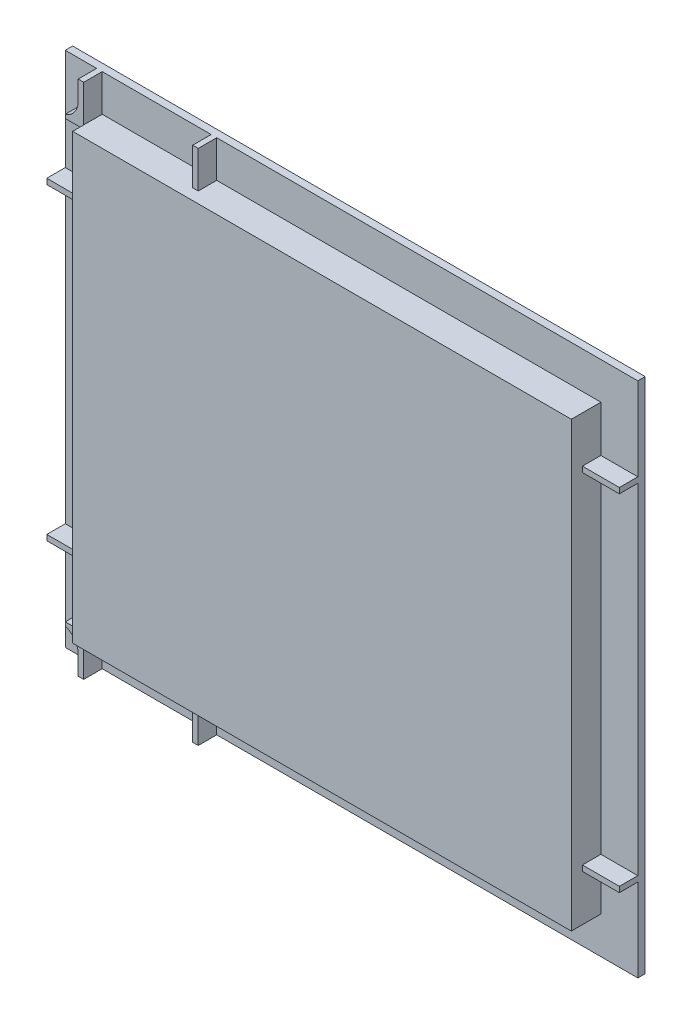
SolidWorks part; units mm, degrees
ref_plane "Front Plane" through (0, 0, 0) normal (0, 0, 1) x (1, 0, 0)
ref_plane "Top Plane" through (0, 0, 0) normal (0, 1, 0) x (1, 0, 0)
ref_plane "Right Plane" through (0, 0, 0) normal (1, 0, 0) x (0, 0, -1)
sketch "Sketch1" plane through (0, 0, 0) normal (0, 0, 1) x (1, 0, 0)
  line L0 (-135, 120) -> (135, 120)
  line L1 (-155, -140) -> (155, -140)
  line L2 (-155, -140) -> (-155, 140)
  line L3 (-155, 140) -> (155, 140)
  line L4 (155, -140) -> (155, 140)
  line L5 (-155, -140) -> (155, 140) construction
  line L6 (-155, 140) -> (155, -140) construction
  line L7 (135, -120) -> (135, 120)
  line L8 (-135, -120) -> (135, -120)
  line L9 (-135, -120) -> (-135, 120)
  point P0 (0, 0)
  dimension "D1" = 310
  dimension "D2" = 280
  dimension "D3" = 20
extrude "Boss-Extrude1" add sketch "Sketch1" along normal blind 4
sketch "Sketch2" plane through (0, 0, 4) normal (0, 0, 1) x (1, 0, 0)
  line L1 (-135, -120) -> (135, -120)
  line L2 (-135, -120) -> (-135, 120)
  line L3 (-135, 120) -> (135, 120)
  line L4 (135, -120) -> (135, 120)
  line L5 (-135, -120) -> (135, 120) construction
  line L6 (-135, 120) -> (135, -120) construction
  line L7 (-131.625, -117) -> (131.625, -117)
  line L8 (-131.625, -117) -> (-131.625, 117)
  line L9 (-131.625, 117) -> (131.625, 117)
  line L10 (131.625, -117) -> (131.625, 117)
  line L11 (-131.625, -117) -> (131.625, 117) construction
  line L12 (-131.625, 117) -> (131.625, -117) construction
  point P0 (0, 0)
  point P5 (0, 0)
  dimension "D1" = 3
extrude "Boss-Extrude3" add sketch "Sketch2" along normal blind 16 and the other way through all
sketch "Sketch4" plane through (0, 0, 20) normal (0, 0, 1) x (1, 0, 0)
  line L1 (-131.625, -117) -> (131.625, -117)
  line L2 (-131.625, -117) -> (-131.625, 117)
  line L3 (-131.625, 117) -> (131.625, 117)
  line L4 (131.625, -117) -> (131.625, 117)
  line L5 (-131.625, -117) -> (131.625, 117) construction
  line L6 (-131.625, 117) -> (131.625, -117) construction
  point P0 (0, 0)
extrude "Boss-Extrude4" add sketch "Sketch4" against normal blind 4
sketch "Sketch6" plane through (0, 0, 4) normal (0, 0, 1) x (1, 0, 0)
  line L0 (155, 0) -> (-155, 0) construction
  line L1 (155, -140) -> (155, 140) construction
  line L2 (-155, 140) -> (-155, -140) construction
  line L3 (155, 95) -> (135, 95) construction
  line L4 (135, -120) -> (135, 120) construction
  line L5 (-155, 82) -> (-135, 82) construction
  line L6 (-135, 120) -> (-135, -120) construction
  line L7 (155, 140) -> (-155, 140) construction
  line L8 (-155, 82) -> (-135, 82)
  line L9 (-155, 82) -> (-155, 85)
  line L10 (-135, 82) -> (-135, 85)
  line L11 (-155, 85) -> (-135, 85)
  line L12 (135, 95) -> (155, 95)
  line L13 (135, 95) -> (135, 92)
  line L14 (155, 95) -> (155, 92)
  line L15 (135, 92) -> (155, 92)
  line L20 (155, -95) -> (155, -92)
  line L21 (135, -92) -> (155, -92)
  line L22 (135, -95) -> (135, -92)
  line L23 (135, -95) -> (155, -95)
  line L28 (-155, -82) -> (-155, -85)
  line L29 (-155, -82) -> (-135, -82)
  line L30 (-155, -85) -> (-135, -85)
  line L31 (-135, -82) -> (-135, -85)
  line L32 (-135, -120) -> (-155, -120) construction
  line L37 (-135, 120) -> (-135, -120) construction
  line L38 (-145, -120) -> (-135, -120)
  line L39 (-145, -120) -> (-145, -118)
  line L40 (-145, -118) -> (-135, -118)
  line L41 (-135, -120) -> (-135, -118)
  line L42 (0, 117.3756) -> (0, -120) construction
  line L47 (-145, 118) -> (-135, 118)
  line L48 (-135, 120) -> (-135, 118)
  line L49 (-145, 120) -> (-135, 120)
  line L50 (-145, 120) -> (-145, 118)
  dimension "D1" = 58
  dimension "D2" = 95
  dimension "D3" = 3
  dimension "D4" = 3
  dimension "D5" = 2
extrude "Boss-Extrude5" add sketch "Sketch6" along normal blind 10
sketch "Sketch7" plane through (0, 0, 4) normal (0, 0, 1) x (1, 0, 0)
  line L0 (-155, 0) -> (155, 0) construction
  line L1 (-155, 82) -> (-155, -82) construction
  line L2 (155, -92) -> (155, 92) construction
  line L3 (-135, 140) -> (-135, 120) construction
  line L4 (155, 140) -> (-155, 140) construction
  line L5 (135, 120) -> (-135, 120) construction
  line L6 (-76, 140) -> (-76, 120) construction
  line L7 (135, 120) -> (-145, 120) construction
  line L8 (-155, 140) -> (-155, 85) construction
  line L9 (-135, 140) -> (-135, 120)
  line L10 (-135, 140) -> (-138, 140)
  line L11 (-135, 120) -> (-138, 120)
  line L12 (-138, 140) -> (-138, 120)
  line L13 (-76, 140) -> (-76, 120)
  line L14 (-76, 140) -> (-73, 140)
  line L15 (-76, 120) -> (-73, 120)
  line L16 (-73, 140) -> (-73, 120)
  line L17 (-135, -120) -> (-138, -120)
  line L18 (-138, -140) -> (-138, -120)
  line L19 (-135, -140) -> (-138, -140)
  line L20 (-135, -140) -> (-135, -120)
  line L21 (-76, -120) -> (-73, -120)
  line L22 (-73, -140) -> (-73, -120)
  line L23 (-76, -140) -> (-73, -140)
  line L24 (-76, -140) -> (-76, -120)
  dimension "D1" = 20
  dimension "D2" = 79
  dimension "D3" = 3
  dimension "D4" = 3
extrude "Boss-Extrude6" add sketch "Sketch7" along normal blind 10 contours L9 L10 L12 L11 | L13 L14 L16 L15 | L17 L18 L19 L20 | L21 L22 L23 L24
fillet "Fillet1" radius 10 2 edges at (-138, -120, 9) (-138, 120, 9)
